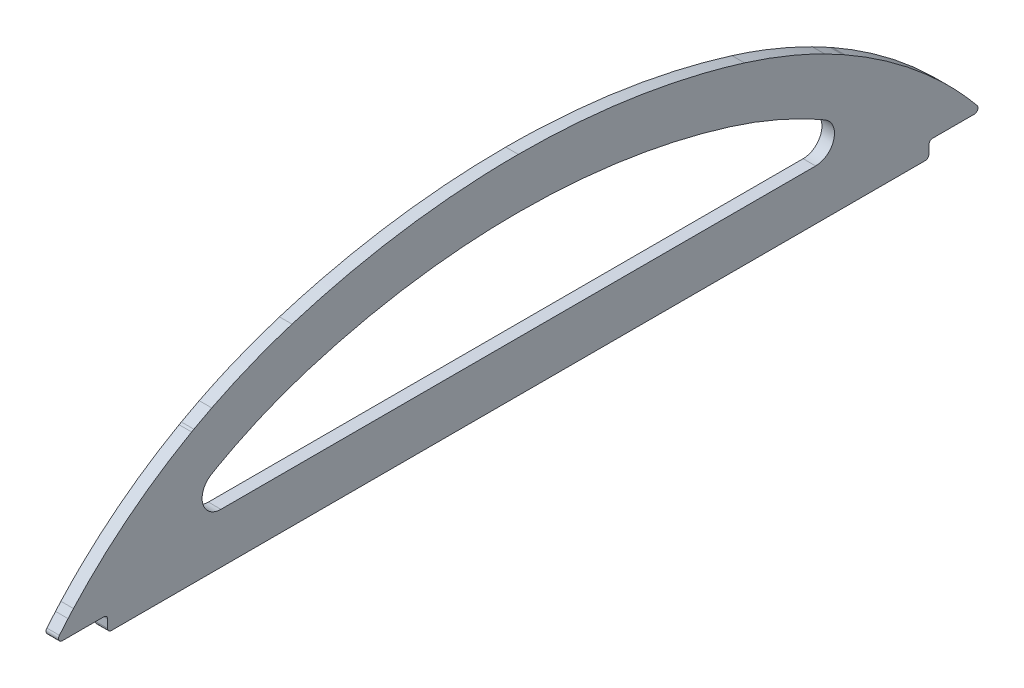
SolidWorks part; units mm, degrees
ref_plane "Front Plane" through (0, 0, 0) normal (0, 0, 1) x (1, 0, 0)
ref_plane "Top Plane" through (0, 0, 0) normal (0, 1, 0) x (1, 0, 0)
ref_plane "Right Plane" through (0, 0, 0) normal (1, 0, 0) x (0, 0, -1)
sketch "Sketch1" plane through (0, 0, 0) normal (1, 0, 0) x (0, 0, -1)
  line L0 (-96.2946, 5.9495) -> (96.2944, 5.9495)
  line L1 (-83.0866, 5.9495) -> (-83.0866, 9.1245)
  line L2 (-83.0866, 9.1245) -> (-93.8548, 9.1245)
  line L3 (83.0869, 5.9495) -> (83.0869, 9.1245)
  line L4 (83.0869, 9.1245) -> (93.8551, 9.1245)
  line L5 (72.5185, 16.1095) -> (-72.5187, 16.1095)
  spline S0 degree 3 poles (96.2944, 5.9495) (95.3162, 7.2776) (94.3159, 8.5664) (93.296, 9.8158) knots 0.775734 0.775734 0.775734 0.775734 1 1 1 1
  spline S1 degree 3 poles (93.296, 9.8158) (92.5735, 10.7008) (91.8374, 11.5701) (91.0886, 12.4237) knots 0 0 0 0 1 1 1 1
  spline S2 degree 3 poles (91.0886, 12.4237) (90.7324, 12.8297) (90.3692, 13.2365) (89.9993, 13.6442) knots 0 0 0 0 0.999999 0.999999 0.999999 0.999999
  spline S3 degree 3 poles (89.9993, 13.6442) (88.2637, 15.5574) (86.4569, 17.3838) (83.6563, 19.9929) (81.8777, 21.5829) (79.9594, 23.172) (79.0037, 23.9336) (78.8802, 24.0316) (78.8501, 24.0555) (74.7664, 27.2888) (70.4984, 30.1374) (66.0898, 32.6255) knots 0 0 0 0 0.25 0.25 0.375 0.484375 0.496094 0.496094 0.5 0.5 1 1 1 1
  spline S4 degree 3 poles (65.6328, 32.882) (64.439, 33.5479) (63.233, 34.1886) (62.0163, 34.8041) knots 0 0 0 0 0.18827 0.18827 0.18827 0.18827
  spline S5 degree 3 poles (66.0898, 32.6255) (65.9377, 32.7114) (65.7854, 32.7968) (65.6328, 32.882) knots 0 0 0 0 0.999999 0.999999 0.999999 0.999999
  spline S6 degree 3 poles (-96.2946, 5.9495) (-96.0496, 6.2797) (-95.5608, 6.9384) (-94.8141, 7.9117) (-94.0613, 8.8716) (-93.5507, 9.5017) (-93.2961, 9.8158) knots 0 0 0 0 0.252116 0.502813 0.752104 1 1 1 1
  spline S7 degree 3 poles (-93.2961, 9.8158) (-93.0545, 10.1097) (-92.5718, 10.6967) (-91.8358, 11.566) (-91.3376, 12.138) (-91.0888, 12.4237) knots 0 0 0 0 0.334016 0.667347 1 1 1 1
  spline S8 degree 3 poles (-91.0888, 12.4237) (-90.9093, 12.6273) (-90.5488, 13.0364) (-90.1831, 13.441) (-89.9995, 13.6442) knots 0 0 0 0 0.497638 1 1 1 1
  spline S9 degree 3 poles (-89.9995, 13.6442) (-89.7316, 13.9372) (-89.1963, 14.5227) (-88.3797, 15.3867) (-87.5543, 16.2391) (-86.7192, 17.0789) (-85.875, 17.9064) (-84.4559, 19.2626) (-82.7167, 20.8423) (-80.9328, 22.3643) (-79.7295, 23.3532) (-78.4521, 24.3773) (-76.7841, 25.6621) (-74.7061, 27.1763) (-72.5966, 28.6308) (-70.4569, 30.0242) (-68.2917, 31.3616) (-66.8231, 32.2047) (-66.09, 32.6255) knots 0 0 0 0 0.03885 0.077625 0.116327 0.154956 0.193513 0.232 0.347035 0.423377 0.461445 0.499444 0.583588 0.667444 0.751013 0.834295 0.917291 1 1 1 1
  spline S10 degree 3 poles (-66.09, 32.6255) (-65.9379, 32.7114) (-65.7855, 32.7968) (-65.6329, 32.882) knots 0 0 0 0 1 1 1 1
  spline S11 degree 3 poles (-65.6329, 32.882) (-65.3341, 33.0475) (-64.7366, 33.3786) (-63.8342, 33.8632) (-62.9282, 34.3396) (-62.3203, 34.6493) (-62.0164, 34.8041) knots 0 0 0 0 0.250232 0.500309 0.750231 1 1 1 1
  spline S12 degree 3 poles (-62.0164, 34.8041) (-61.1402, 35.2383) (-59.3888, 36.106) (-56.7181, 37.3111) (-54.0212, 38.445) (-51.2966, 39.499) (-48.5499, 40.4818) (-46.6986, 41.0723) (-45.7736, 41.3673) knots 0 0 0 0 0.167265 0.334295 0.501086 0.667635 0.83394 1 1 1 1
  spline S13 degree 3 poles (-45.7736, 41.3673) (-44.5402, 41.7394) (-42.0735, 42.4836) (-38.3385, 43.4787) (-34.5811, 44.385) (-30.8008, 45.1942) (-27.0006, 45.9085) (-23.1821, 46.5276) (-19.3476, 47.0516) (-15.4988, 47.4802) (-11.6376, 47.8142) (-7.7659, 48.0509) (-3.8856, 48.199) (-1.2957, 48.2167) (0, 48.2256) knots 0 0 0 0 0.083186 0.16637 0.249558 0.332759 0.415981 0.499234 0.582527 0.665873 0.749281 0.832764 0.916333 1 1 1 1
  spline S14 degree 3 poles (0, 48.2256) (1.2957, 48.2167) (3.8856, 48.199) (7.7659, 48.0509) (11.6376, 47.8142) (15.4987, 47.4802) (19.3475, 47.0516) (23.1821, 46.5276) (27.0005, 45.9085) (30.8007, 45.1941) (34.581, 44.385) (38.3384, 43.4787) (42.0734, 42.4836) (44.5401, 41.7394) (45.7734, 41.3673) knots 0 0 0 0 0.083667 0.167236 0.250719 0.334127 0.417473 0.500766 0.584019 0.667241 0.750442 0.83363 0.916814 1 1 1 1
  spline S15 degree 3 poles (45.7734, 41.3673) (46.6984, 41.0723) (48.5497, 40.4818) (51.2965, 39.499) (54.0211, 38.445) (56.718, 37.3111) (59.3887, 36.106) (61.14, 35.2383) (62.0163, 34.8041) knots 0 0 0 0 0.16606 0.332365 0.498914 0.665705 0.832735 1 1 1 1
  spline S26 degree 3 poles (-82.5005, 6.7892) (-82.2976, 7.0111) (-81.8761, 7.4722) (-81.3314, 8.054) (-80.7305, 8.6819) (-79.5477, 9.893) (-77.1002, 12.2713) (-74.3071, 14.695) (-71.6232, 16.8205) (-69.5673, 18.3671) (-67.4583, 19.8435) (-65.545, 21.1) (-64.3225, 21.8715) (-63.3625, 22.4571) (-62.6461, 22.8824) (-61.883, 23.3255) (-61.3348, 23.6402) (-61.0655, 23.7948) knots 0 0 0 0 0.03121 0.062421 0.093631 0.124842 0.249684 0.467905 0.530326 0.624209 0.749051 0.811472 0.873893 0.905103 0.936313 0.967524 0.998734 0.998734 0.998734 0.998734
  spline S27 degree 3 poles (-61.0655, 23.7948) (-61.0347, 23.8122) (-60.9732, 23.8468) (-60.8808, 23.8987) (-60.7883, 23.9505) (-60.7265, 23.9851) (-60.6956, 24.0023) knots 0.077726 0.077726 0.077726 0.077726 0.300433 0.523141 0.745848 0.968556 0.968556 0.968556 0.968556
  spline S28 degree 3 poles (-60.6956, 24.0023) (-60.5539, 24.0808) (-60.2624, 24.2422) (-59.7437, 24.5274) (-59.085, 24.8812) (-58.417, 25.2328) (-57.894, 25.5017) (-57.5985, 25.6524) (-57.4549, 25.7255) knots 0.003841 0.003841 0.003841 0.003841 0.126618 0.249395 0.494948 0.740501 0.863278 0.986054 0.986054 0.986054 0.986054
  spline S29 degree 3 poles (-57.4549, 25.7255) (-57.1384, 25.8823) (-56.4946, 26.2012) (-55.5903, 26.643) (-54.7306, 27.0521) (-53.5649, 27.5878) (-52.0522, 28.2524) (-50.2407, 29.007) (-48.4136, 29.722) (-46.8612, 30.2954) (-45.6454, 30.7221) (-44.7404, 31.0266) (-43.7827, 31.3379) (-43.0988, 31.5562) (-42.7624, 31.6635) knots 0.003251 0.003251 0.003251 0.003251 0.065263 0.127274 0.189286 0.251298 0.375321 0.499344 0.623367 0.74739 0.809401 0.871413 0.933424 0.995436 0.995436 0.995436 0.995436
  spline S30 degree 3 poles (-42.7624, 31.6635) (-42.3088, 31.8003) (-41.3911, 32.077) (-40.0755, 32.4668) (-38.8039, 32.8301) (-37.0888, 33.2976) (-34.8955, 33.8597) (-31.3915, 34.6916) (-26.9816, 35.6043) (-21.6471, 36.502) (-16.2801, 37.1998) (-11.79, 37.616) (-8.1875, 37.8477) (-5.921, 37.9544) (-4.1384, 38.0121) (-2.8096, 38.0395) (-1.4333, 38.0554) (-0.4743, 38.0621) (0, 38.0653) knots 0.001722 0.001722 0.001722 0.001722 0.032872 0.064021 0.095171 0.12632 0.188619 0.250918 0.375516 0.500113 0.624711 0.749309 0.811608 0.873907 0.905056 0.936206 0.967355 0.998505 0.998505 0.998505 0.998505
  spline S31 degree 3 poles (0, 38.0653) (0.4743, 38.0621) (1.4333, 38.0554) (2.8096, 38.0395) (4.1384, 38.0121) (5.9209, 37.9544) (8.1875, 37.8477) (11.7899, 37.616) (16.28, 37.1998) (21.6471, 36.502) (26.9815, 35.6043) (31.3914, 34.6916) (34.8954, 33.8597) (37.0887, 33.2976) (38.8037, 32.8301) (40.0754, 32.4668) (41.3909, 32.077) (42.3086, 31.8003) (42.7622, 31.6635) knots 0.001495 0.001495 0.001495 0.001495 0.032645 0.063794 0.094944 0.126093 0.188392 0.250691 0.375289 0.499887 0.624484 0.749082 0.811381 0.87368 0.90483 0.935979 0.967128 0.998278 0.998278 0.998278 0.998278
  spline S32 degree 3 poles (42.7622, 31.6635) (43.0989, 31.5561) (43.7833, 31.3376) (44.7417, 31.0261) (45.6473, 30.7213) (46.8641, 30.2943) (48.4178, 29.7204) (50.2461, 29.0048) (52.0591, 28.2494) (53.5729, 27.5841) (54.7391, 27.0481) (55.5998, 26.6384) (56.5052, 26.1958) (57.1498, 25.8766) (57.4668, 25.7195) knots 0.004564 0.004564 0.004564 0.004564 0.066624 0.128683 0.190743 0.252802 0.376922 0.501041 0.62516 0.749279 0.811339 0.873398 0.935458 0.997518 0.997518 0.997518 0.997518
  spline S33 degree 3 poles (57.4668, 25.7195) (57.7376, 25.5824) (58.2778, 25.3055) (59.0839, 24.882) (59.8859, 24.4504) (60.4176, 24.1573) (60.6828, 24.0094) knots 0.000025 0.000025 0.000025 0.000025 0.046559 0.093093 0.139626 0.18616 0.18616 0.18616 0.18616
  spline S34 degree 3 poles (60.6828, 24.0094) (60.7174, 23.9901) (60.7866, 23.9514) (60.8902, 23.8934) (60.9936, 23.8353) (61.0624, 23.7965) (61.0968, 23.7771) knots 0.001594 0.001594 0.001594 0.001594 0.250933 0.500272 0.749611 0.998951 0.998951 0.998951 0.998951
  spline S35 degree 3 poles (61.0968, 23.7771) (63.0869, 22.6538) (66.004, 20.858) (69.6507, 18.3105) (71.617, 16.8241) (72.9748, 15.7485) (73.9468, 14.9589) (75.5712, 13.5924) (78.5305, 10.9467) (80.9502, 8.4997) (82.4841, 6.8087) knots 0 0 0 0 0.249993 0.37499 0.484672 0.515921 0.562484 0.624983 0.749979 0.999972 0.999972 0.999972 0.999972
  point P5 (0, 0)
  point P38 (0, 0)
  dimension "D1" = 192.5891
  dimension "D2" = 3.175
  dimension "D3" = 13.208
  dimension "D5" = 10.16
extrude "Boss-Extrude1" add sketch "Sketch1" along normal blind 2.54 contours S15 S14 S13 S12 S11 S10 S9 S8 S7 S6 L2 L1 L0 L3 L4 S0 S1 S2 S3 S5 S4 S34 S35 L5 S26 S27 S28 S29 S30 S31 S32 S33 region at (0, 7.537, 81.1625)
fillet "Fillet1" radius 3.81 2 edges at (1.27, 16.1095, -72.5185) (1.27, 16.1095, 72.5187)
fillet "Fillet2" radius 0.762 6 edges at (1.27, 5.9495, 83.0866) (1.27, 9.1245, 83.0866) (1.27, 9.1245, -83.0869) (1.27, 5.9495, -83.0869)
